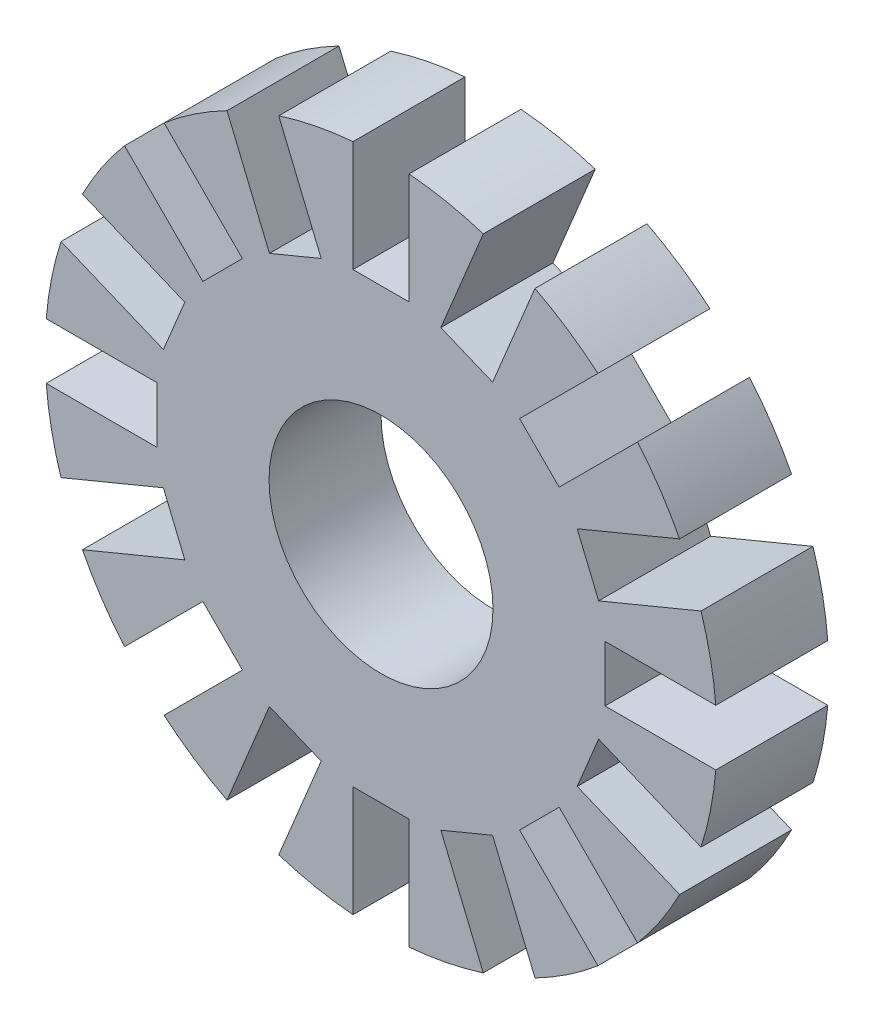
SolidWorks part; units mm, degrees
ref_plane "Front Plane" through (0, 0, 0) normal (0, 0, 1) x (1, 0, 0)
ref_plane "Top Plane" through (0, 0, 0) normal (0, 1, 0) x (1, 0, 0)
ref_plane "Right Plane" through (0, 0, 0) normal (1, 0, 0) x (0, 0, -1)
sketch "Sketch1" plane through (0, 0, 0) normal (0, 0, 1) x (1, 0, 0)
  line L0 (1.5875, 18.9837) -> (1.5875, 12.7)
  line L1 (1.5875, 12.7) -> (-1.5875, 12.7)
  line L2 (-1.5875, 12.7) -> (-1.5875, 18.9837)
  line L3 (0, 0) -> (0, 12.7) construction
  line L4 (0, 0) -> (4.8601, 11.7333) construction
  line L5 (3.3934, 12.3408) -> (5.7981, 18.1462)
  line L6 (6.3267, 11.1258) -> (3.3934, 12.3408)
  line L7 (8.7314, 16.9312) -> (6.3267, 11.1258)
  line L8 (0, 0) -> (8.9803, 8.9803) construction
  line L9 (7.8577, 10.1028) -> (12.301, 14.5461)
  line L10 (10.1028, 7.8577) -> (7.8577, 10.1028)
  line L11 (14.5461, 12.301) -> (10.1028, 7.8577)
  line L12 (0, 0) -> (11.7333, 4.8601) construction
  line L13 (11.1258, 6.3267) -> (16.9312, 8.7314)
  line L14 (12.3408, 3.3934) -> (11.1258, 6.3267)
  line L15 (18.1462, 5.7981) -> (12.3408, 3.3934)
  line L16 (0, 0) -> (12.7, 0) construction
  line L17 (12.7, 1.5875) -> (18.9837, 1.5875)
  line L18 (12.7, -1.5875) -> (12.7, 1.5875)
  line L19 (18.9837, -1.5875) -> (12.7, -1.5875)
  line L20 (0, 0) -> (11.7333, -4.8601) construction
  line L21 (12.3408, -3.3934) -> (18.1462, -5.7981)
  line L22 (11.1258, -6.3267) -> (12.3408, -3.3934)
  line L23 (16.9312, -8.7314) -> (11.1258, -6.3267)
  line L24 (0, 0) -> (8.9803, -8.9803) construction
  line L25 (10.1028, -7.8577) -> (14.5461, -12.301)
  line L26 (7.8577, -10.1028) -> (10.1028, -7.8577)
  line L27 (12.301, -14.5461) -> (7.8577, -10.1028)
  line L28 (0, 0) -> (4.8601, -11.7333) construction
  line L29 (6.3267, -11.1258) -> (8.7314, -16.9312)
  line L30 (3.3934, -12.3408) -> (6.3267, -11.1258)
  line L31 (5.7981, -18.1462) -> (3.3934, -12.3408)
  line L32 (0, 0) -> (0, -12.7) construction
  line L33 (1.5875, -12.7) -> (1.5875, -18.9837)
  line L34 (-1.5875, -12.7) -> (1.5875, -12.7)
  line L35 (-1.5875, -18.9837) -> (-1.5875, -12.7)
  line L36 (0, 0) -> (-4.8601, -11.7333) construction
  line L37 (-3.3934, -12.3408) -> (-5.7981, -18.1462)
  line L38 (-6.3267, -11.1258) -> (-3.3934, -12.3408)
  line L39 (-8.7314, -16.9312) -> (-6.3267, -11.1258)
  line L40 (0, 0) -> (-8.9803, -8.9803) construction
  line L41 (-7.8577, -10.1028) -> (-12.301, -14.5461)
  line L42 (-10.1028, -7.8577) -> (-7.8577, -10.1028)
  line L43 (-14.5461, -12.301) -> (-10.1028, -7.8577)
  line L44 (0, 0) -> (-11.7333, -4.8601) construction
  line L45 (-11.1258, -6.3267) -> (-16.9312, -8.7314)
  line L46 (-12.3408, -3.3934) -> (-11.1258, -6.3267)
  line L47 (-18.1462, -5.7981) -> (-12.3408, -3.3934)
  line L48 (0, 0) -> (-12.7, 0) construction
  line L49 (-12.7, -1.5875) -> (-18.9837, -1.5875)
  line L50 (-12.7, 1.5875) -> (-12.7, -1.5875)
  line L51 (-18.9837, 1.5875) -> (-12.7, 1.5875)
  line L52 (0, 0) -> (-11.7333, 4.8601) construction
  line L53 (-12.3408, 3.3934) -> (-18.1462, 5.7981)
  line L54 (-11.1258, 6.3267) -> (-12.3408, 3.3934)
  line L55 (-16.9312, 8.7314) -> (-11.1258, 6.3267)
  line L56 (0, 0) -> (-8.9803, 8.9803) construction
  line L57 (-10.1028, 7.8577) -> (-14.5461, 12.301)
  line L58 (-7.8577, 10.1028) -> (-10.1028, 7.8577)
  line L59 (-12.301, 14.5461) -> (-7.8577, 10.1028)
  line L60 (0, 0) -> (-4.8601, 11.7333) construction
  line L61 (-6.3267, 11.1258) -> (-8.7314, 16.9312)
  line L62 (-3.3934, 12.3408) -> (-6.3267, 11.1258)
  line L63 (-5.7981, 18.1462) -> (-3.3934, 12.3408)
  circle A0 centre (0, 0) radius 19.05
  circle A1 centre (0, 0) radius 6.35
  point P86 (0, 0)
  dimension "D2" = 38.1
  dimension "D5" = 12.7
  dimension "D1" = 3.175
  dimension "D3" = 12.7
  dimension "D4" = 16
extrude "Boss-Extrude1" add sketch "Sketch1" along normal blind 3.175 and the other way blind 3.175 contours A0 L0 L1 L2 region at (3.6117, 18.1573, 0)
